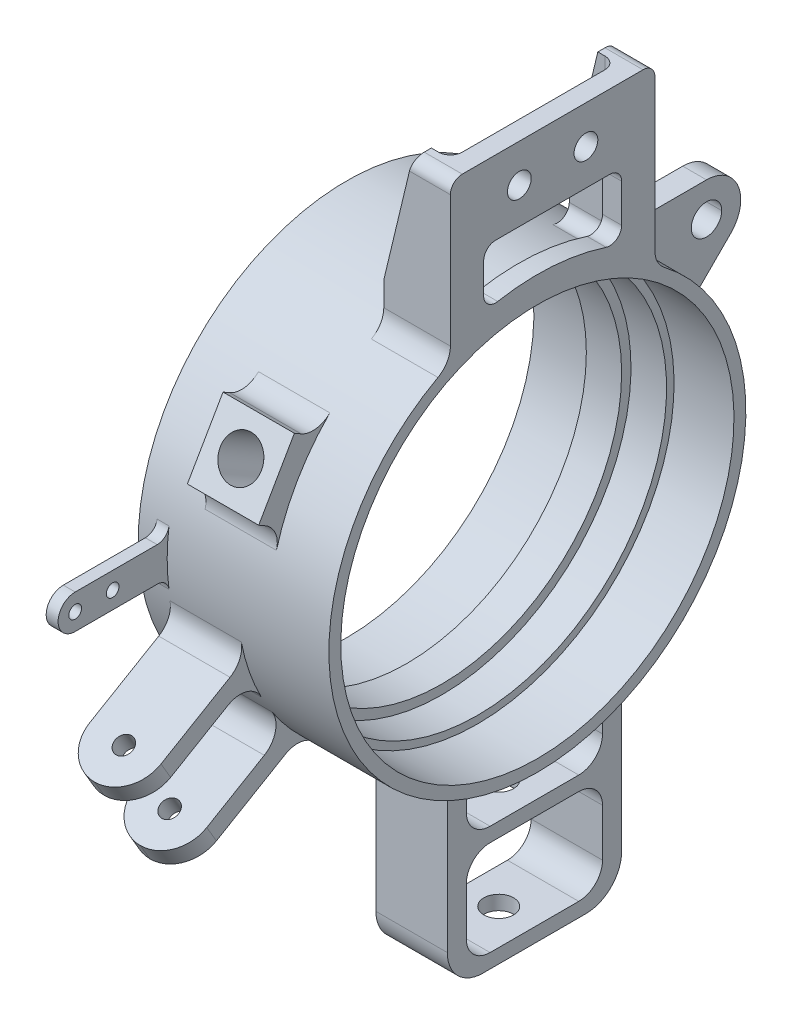
SolidWorks part; units mm, degrees
other "Markup1"
sketch "Sketch14" plane through (58.951, 102.625, 76.2) normal (1, 0, 0) x (0, 1, 0)
sketch "Sketch22" plane through (47.925, 102.625, 82.3041) normal (1, 0, 0) x (0, 1, 0)
sketch "Sketch23" plane through (50.925, 100.125, 82.3041) normal (1, 0, 0) x (0, 1, 0)
sketch "Sketch25" plane through (50.925, 100.125, 82.3041) normal (1, 0, 0) x (0, 1, 0)
sketch "Sketch27" plane through (50.925, 100.125, 82.3041) normal (1, 0, 0) x (0, 1, 0)
sketch "Sketch33" plane through (50.925, 92.71, 84.805) normal (1, 0, 0) x (0, 1, 0)
sketch "Sketch36" plane through (50.925, 92.71, 84.805) normal (1, 0, 0) x (0, 1, 0)
material "7075-T6 (SN)"
ref_plane "Front Plane" through (0, 0, 0) normal (0, 0, 1) x (1, 0, 0)
ref_plane "Top Plane" through (0, 0, 0) normal (0, 1, 0) x (1, 0, 0)
ref_plane "Right Plane" through (0, 0, 0) normal (1, 0, 0) x (0, 0, -1)
sketch "Sketch1" plane through (0, 0, 0) normal (0, 0, 1) x (1, 0, 0)
  line L0 (50.925, 0) -> (0, 0) construction
  line L1 (50.925, 52.5) -> (34.925, 52.5)
  line L2 (34.925, 52.5) -> (34.925, 50.5)
  line L3 (25.425, 48) -> (16, 48)
  line L4 (16, 48) -> (16, 50)
  line L5 (16, 50) -> (0, 50)
  line L6 (50.925, 52.5) -> (50.925, 55.675)
  line L7 (50.925, 55.675) -> (0, 55.675)
  line L8 (0, 55.675) -> (0, 50)
  line L9 (42.925, 52.5) -> (60.451, 52.5) construction
  line L10 (34.925, 50.5) -> (25.425, 50.5)
  line L11 (25.425, 50.5) -> (25.425, 48)
  point P11 (8, 50)
  point P12 (42.925, 52.5)
  dimension "D1" = 52.5
  dimension "D2" = 2
  dimension "D3" = 16
  dimension "D4" = 34.925
  dimension "D5" = 3.175
  dimension "D6" = 17.526
  dimension "D7" = 50
  dimension "D8" = 2
  dimension "D9" = 9.5
revolve "Revolve1" add sketch "Sketch1" angle 360 about L0
ref_plane "upper a-arm plane" through (0, 55.675, 0) normal (0, 1, 0) x (1, 0, 0)
ref_plane "rear tierod plane" through (0, 0, 76.2) normal (0, 0, 1) x (1, 0, 0)
sketch "Sketch4" plane through (0, 55.675, 0) normal (0, 1, 0) x (1, 0, 0)
  line L0 (45.845, 26.2995) -> (45.845, -18.1505)
  line L1 (45.845, -18.1505) -> (33.145, -18.1505)
  line L2 (33.145, -18.1505) -> (33.145, -23.2305)
  line L3 (33.145, -23.2305) -> (50.925, -23.2305)
  line L4 (50.925, -23.2305) -> (50.925, 31.3795)
  line L5 (50.925, 31.3795) -> (33.145, 31.3795)
  line L6 (33.145, 31.3795) -> (33.145, 26.2995)
  line L7 (33.145, 26.2995) -> (45.845, 26.2995)
  line L8 (50.925, 0) -> (0, 0) construction
  line L10 (50.925, -55.675) -> (50.925, 55.675) construction
  point P13 (45.845, 4.0745)
  dimension "D1" = 44.45
  dimension "D2" = 5.08
  dimension "D3" = 5.08
  dimension "D4" = 4.0745
  dimension "D5" = 12.7
extrude "Boss-Extrude2" add sketch "Sketch4" along normal blind 37.035 and the other way up to surface other way up to face at (0, -55.675, 0)
ref_plane "Plane3" through (0, -55.675, 0) normal (0, -1, 0) x (-1, 0, 0)
sketch "Sketch10" plane through (31.5204, 0, 0) normal (-1, 0, 0) x (0, 0, 1)
  line L2 (-64.565, -30.226) -> (0, 0) construction
  line L3 (0, 0) -> (-64.565, 30.226) construction
  line L6 (-64.565, 30.226) -> (-73.709, 30.226) construction
  line L7 (-64.565, -30.226) -> (-73.709, -30.226) construction
  line L9 (-64.565, 39.37) -> (-39.3663, 39.37)
  line L10 (-55.125, 7.8063) -> (-71.0405, 23.77)
  line L11 (-62.9636, -39.2287) -> (-42.7748, -35.6374)
  line L20 (-64.565, -30.226) -> (-64.565, 30.226) construction
  line L21 (0, 0) -> (-64.565, 0) construction
  line L22 (-71.0405, -23.77) -> (-55.125, -7.8063)
  circle A0 centre (-64.565, -30.226) radius 4.064 construction
  circle A1 centre (-64.565, -30.226) radius 4.064
  circle A2 centre (-64.565, 30.226) radius 4.064 construction
  circle A3 centre (-64.565, 30.226) radius 4.064
  arc A6 (-71.0405, -23.77) -> (-62.9636, -39.2287) centre (-64.565, -30.226) ccw
  arc A7 (-64.565, 39.37) -> (-71.0405, 23.77) centre (-64.565, 30.226) ccw
  circle A9 centre (0, 0) radius 55.675 construction
  arc A10 (-55.125, -7.8063) -> (-42.7748, -35.6374) centre (0, 0) ccw
  arc A11 (-39.3663, 39.37) -> (-55.125, 7.8063) centre (0, 0) ccw
  dimension "D1" = 5.08
  dimension "D2" = 5.08
  dimension "D3" = 20
  dimension "D4" = 20
  dimension "D5" = 15
extrude "Boss-Extrude5" add sketch "Sketch10" along normal blind 6.35
sketch "Sketch12" plane through (50.925, 0, 0) normal (1, 0, 0) x (0, 0, -1)
  line L0 (12.9645, 82.55) -> (-4.8155, 82.55) construction
  line L1 (-23.2305, 92.71) -> (31.3795, 92.71) construction
  circle A0 centre (-4.8155, 82.55) radius 3.175
  circle A1 centre (12.9645, 82.55) radius 3.175
  point P6 (4.0745, 92.71)
  point P7 (4.0745, 82.55)
  dimension "D1" = 6.35
  dimension "D2" = 17.78
  dimension "D3" = 10.16
extrude "Cut-Extrude5" cut sketch "Sketch12" against normal through all
ref_plane "Plane4" through (0, 30.226, 0) normal (0, 1, 0) x (1, 0, 0)
ref_plane "Plane5" through (0, -30.226, 0) normal (0, 1, 0) x (1, 0, 0)
split line "Split Line1"
split line "Split Line2"
ref_plane "tierod 2" through (17.0573, 0, 0) normal (-1, 0, 0) x (0, 0, 1)
ref_plane "Plane6" through (25.4625, 0, 0) normal (-1, 0, 0) x (0, 0, 1)
sketch "Sketch18" plane through (25.4625, 0, 0) normal (-1, 0, 0) x (0, 0, 1)
  line L5 (0, 0) -> (53.7152, 31.0125) construction
  line L6 (0, 0) -> (55.675, 0) construction
  line L7 (48.9527, 39.2614) -> (58.4777, 22.7636)
  line L8 (48.9527, 39.2614) -> (42.7426, 35.676)
  line L9 (58.4777, 22.7636) -> (52.2676, 19.1782)
  circle A1 centre (0, 0) radius 55.675 construction
  arc A2 (52.2676, 19.1782) -> (42.7426, 35.676) centre (0, 0) ccw
  point P17 (48.216, 27.8375)
  point P20 (53.7152, 31.0125)
  dimension "D4" = 30
  dimension "D5" = 19.05
  dimension "D6" = 6.35
extrude "Boss-Extrude7" add sketch "Sketch18" along normal blind 9.525 and the other way blind 9.525
sketch "Sketch19" plane through (0, 31.0125, 53.7152) normal (0, 0.5, 0.866) x (1, 0, 0)
  line L0 (34.9875, -9.525) -> (34.9875, 9.525) construction
  line L1 (34.9875, 9.525) -> (15.9375, 9.525) construction
  circle A0 centre (25.4625, 0) radius 5.5
  point P5 (34.9875, 0)
  point P8 (25.4625, 9.525)
  dimension "D1" = 11
extrude "Cut-Extrude7" cut sketch "Sketch19" against normal up to next
sketch "Sketch21" plane through (50.925, 0, 0) normal (1, 0, 0) x (0, 0, -1)
  line L0 (-14.3405, 61.6572) -> (-14.3405, 69.7955)
  line L1 (-11.1655, 72.9705) -> (19.3145, 72.9705)
  line L2 (22.4895, 69.7955) -> (22.4895, 59.6089)
  line L5 (26.2995, 92.71) -> (26.2995, 49.0718) construction
  line L6 (-18.1505, 92.71) -> (-18.1505, 52.6333) construction
  arc A0 (-10.5998, 58.533) -> (18.3358, 56.5885) centre (0, 0) cw
  circle A1 centre (0, 0) radius 55.675 construction
  arc A2 (19.3145, 72.9705) -> (22.4895, 69.7955) centre (19.3145, 69.7955) cw
  arc A3 (22.4895, 59.6089) -> (18.3358, 56.5885) centre (19.3145, 59.6089) cw
  arc A4 (-14.3405, 61.6572) -> (-10.5998, 58.533) centre (-11.1655, 61.6572) ccw
  arc A5 (-14.3405, 69.7955) -> (-11.1655, 72.9705) centre (-11.1655, 69.7955) cw
  point P19 (-14.3405, 57.7305)
  point P22 (-14.3405, 72.9705)
  dimension "D3" = 3.81
  dimension "D5" = 3.175
  dimension "D1" = 3.81
  dimension "D2" = 3.81
  dimension "D4" = 15.24
sketch "Sketch24" plane through (0, -55.675, 0) normal (0, -1, 0) x (-1, 0, 0)
  line L0 (0, -50) -> (0, 50) construction
  line L1 (-36.7423, 36.6591) -> (-17.6923, 36.6591)
  line L2 (-36.7423, 36.6591) -> (-36.7423, -9.8739)
  line L3 (-36.7423, -9.8739) -> (-17.6923, -9.8739)
  line L4 (-17.6923, 36.6591) -> (-17.6923, -9.8739)
  line L5 (-36.7423, 36.6591) -> (-17.6923, -9.8739) construction
  line L6 (-36.7423, -9.8739) -> (-17.6923, 36.6591) construction
  line L7 (-50.925, 0) -> (0, 0) construction
  point P0 (-27.2173, 13.3926)
  dimension "D1" = 27.2173
  dimension "D2" = 13.3926
  dimension "D3" = 46.533
  dimension "D4" = 19.05
extrude "Boss-Extrude10" add sketch "Sketch24" against normal up to surface and the other way blind 53.34 up to face at (28.3454, -22.1522, -49.9197)
sketch "Sketch29" plane through (36.7423, 0, 0) normal (1, 0, 0) x (0, 0, -1)
  line L0 (36.6591, -109.015) -> (-9.8739, -109.015) construction
  line L1 (-4.7939, -79.805) -> (31.5791, -79.805)
  line L2 (-4.7939, -79.805) -> (-4.7939, -105.205)
  line L3 (-4.7939, -105.205) -> (31.5791, -105.205)
  line L4 (31.5791, -79.805) -> (31.5791, -105.205)
  line L5 (-9.8739, -109.015) -> (-9.8739, -54.7924) construction
  line L6 (13.3926, -109.015) -> (13.3926, -95.25) construction
  line L8 (-4.7939, -58.6544) -> (-4.7939, -75.995)
  line L9 (31.5791, -75.995) -> (31.5791, -49.6597)
  line L10 (-4.7939, -75.995) -> (31.5791, -75.995)
  arc A0 (-4.7939, -58.6544) -> (31.5791, -49.6597) centre (0, 0) ccw
  arc A4 (-9.8739, -54.7924) -> (36.6591, -41.9025) centre (0, 0) ccw construction
  point P6 (13.3926, -109.015)
  point P7 (13.3926, -105.205)
  dimension "D6" = 3.175
  dimension "D1" = 25.4
  dimension "D2" = 3.81
  dimension "D3" = 5.08
  dimension "D4" = 13.765
  dimension "D5" = 3.81
  dimension "D7" = 5.08
extrude "Cut-Extrude12" cut sketch "Sketch29" against normal up to next
sketch "Sketch26" plane through (0, -109.015, 0) normal (0, -1, 0) x (1, 0, 0)
  line L0 (36.7423, -36.6591) -> (36.7423, 9.8739) construction
  line L1 (17.6923, -36.6591) -> (36.7423, -36.6591) construction
  circle A0 centre (27.2173, -13.3926) radius 3.9688
  point P4 (36.7423, -13.3926)
  point P7 (27.2173, -36.6591)
  dimension "D1" = 7.9375
extrude "Cut-Extrude11" cut sketch "Sketch26" against normal up to surface (33.02 mm away) up to face at (27.2173, -75.995, -13.3926)
sketch "Sketch30" plane through (0, 0, 23.2305) normal (0, 0, 1) x (1, 0, 0)
  line L1 (33.145, 92.71) -> (33.145, 50.5969) construction
  line L2 (33.145, 60.96) -> (40.765, 92.71)
  line L3 (33.145, 92.71) -> (50.925, 92.71) construction
extrude "Cut-Extrude13" cut sketch "Sketch30" against normal through all
extrude "Cut-Extrude14" cut sketch "Sketch21" against normal up to next
ref_plane "Plane7" through (7.745, 0, 0) normal (1, 0, 0) x (0, 0, -1)
sketch "Sketch32" plane through (7.745, 0, 0) normal (1, 0, 0) x (0, 0, -1)
  line L0 (-80.233, -4.572) -> (-55.487, -4.572)
  line L1 (-80.233, 4.572) -> (-55.487, 4.572)
  line L2 (-80.233, 0) -> (-70.233, 0) construction
  line L3 (0, 0) -> (-55.675, 0) construction
  arc A0 (-23.2305, 50.5969) -> (31.3795, 45.9895) centre (0, 0) ccw construction
  arc A1 (-55.487, 4.572) -> (-55.487, -4.572) centre (0, 0) ccw
  arc A2 (-80.233, 4.572) -> (-80.233, -4.572) centre (-80.233, 0) ccw
  circle A3 centre (-80.233, 0) radius 1.7
  circle A4 centre (-70.233, 0) radius 1.7
  point P11 (-75.233, 0)
  dimension "D2" = 3.4
  dimension "D1" = 10
  dimension "D3" = 19.558
  dimension "D4" = 4.572
extrude "Boss-Extrude11" add sketch "Sketch32" against normal blind 3.175
sketch "Sketch34" plane through (17.0573, 0, 0) normal (-1, 0, 0) x (0, 0, 1)
  line L0 (0, 0) -> (69.1574, 0) construction
  line L1 (50, 0) -> (-50, 0) construction
  line L2 (69.1574, 0) -> (69.1574, -40.64) construction
  line L3 (69.1574, -40.64) -> (0, 0) construction
  line L4 (81.8036, -37.0236) -> (52.1186, -19.5794)
  line L5 (72.1521, -53.4477) -> (42.4671, -36.0035)
  line L6 (81.8036, -37.0236) -> (84.3773, -32.6438)
  line L7 (84.3773, -32.6438) -> (53.7191, -14.6277)
  line L8 (72.1521, -53.4477) -> (69.5783, -57.8274)
  line L9 (69.5783, -57.8274) -> (38.9201, -39.8112)
  circle A0 centre (0, 0) radius 55.675 construction
  arc A1 (38.9201, -39.8112) -> (42.4671, -36.0035) centre (0, 0) ccw
  arc A2 (52.1186, -19.5794) -> (53.7191, -14.6277) centre (0, 0) ccw
  dimension "D1" = 69.1574
  dimension "D2" = 40.64
  dimension "D3" = 5.08
  dimension "D4" = 19.05
  dimension "D5" = 9.525
  dimension "D6" = 35.56
extrude "Boss-Extrude12" add sketch "Sketch34" along normal blind 9.525 and the other way blind 9.525
sketch "Sketch35" plane through (0, 12.5918, 7.3995) normal (0, 0.8622, 0.5066) x (1, 0, 0)
  circle A0 centre (17.0573, -80.2145) radius 2.3813
  point P0 (17.0573, -80.2145)
  dimension "D1" = 4.7625
extrude "Cut-Extrude15" cut sketch "Sketch35" against normal up to surface (29.21 mm away) up to face at (17.0573, -48.8193, 54.2492)
fillet "0.125\" fillets" radius 3.175 13 edges at (28.3454, -35.6374, -42.7748) (28.3454, 39.37, -39.3663) (28.3454, 7.8063, -55.125) (28.3454, -7.8063, -55.125) (39.495, 52.6333, 18.1505) (45.845, 55.4971, -4.4466) (39.495, 49.0718, -26.2995) (45.845, 72.6716, 18.1505) (45.845, 70.8909, -26.2995) (45.845, 92.71, -31.3795) (45.845, 92.71, 23.2305) (6.1575, -4.572, 55.487) (6.1575, 4.572, 55.487)
fillet "0.375\" fillets" radius 9.525 6 edges at (27.2173, -109.015, -36.6591) (27.2173, -109.015, 9.8739) (26.5823, -55.6376, 70.8652) (7.5323, -55.6376, 70.8652) (7.5323, -34.8337, 83.0905) (26.5823, -34.8337, 83.0905)
fillet "Fillet1" radius 6.35 18 edges at (25.4625, 19.1782, 52.2676) (25.4625, 35.676, 42.7426) (42.035, 50.5969, 23.2305) (42.035, 45.9895, -31.3795) (27.2173, -49.6597, -31.5791) (27.2173, -79.805, -31.5791) (27.2173, -105.205, -31.5791) (27.2173, -75.995, -31.5791) (27.2173, -58.6544, 4.7939) (27.2173, -79.805, 4.7939) (27.2173, -75.995, 4.7939) (27.2173, -105.205, 4.7939) (27.2173, -41.9025, -36.6591) (27.2173, -54.7924, 9.8739) (17.0573, -39.8112, 38.9201) (17.0573, -36.0035, 42.4671) (17.0573, -19.5794, 52.1186) (17.0573, -14.6277, 53.7191)
